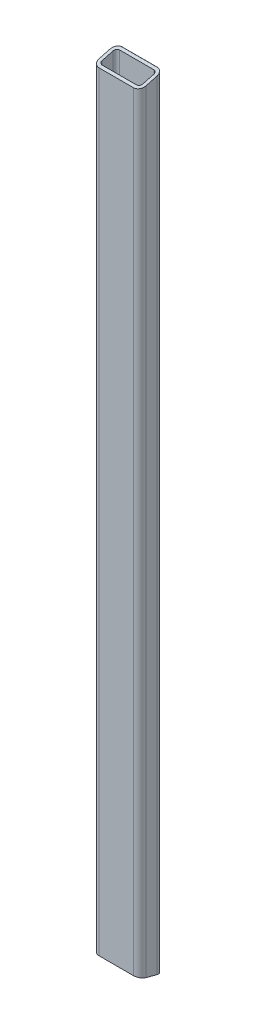
SolidWorks part; units mm, degrees
material "Ст 3 ГОСТ 380-88"
ref_plane "Спереди" through (0, 0, 0) normal (0, 0, 1) x (1, 0, 0)
ref_plane "Сверху" through (0, 0, 0) normal (0, 1, 0) x (1, 0, 0)
ref_plane "Справа" through (0, 0, 0) normal (1, 0, 0) x (0, 0, -1)
sketch "Эскиз1" plane through (0, 0, 0) normal (0, 1, 0) x (1, 0, 0)
  line L0 (-15, 7.5) -> (15, -7.5) construction
  line L1 (-11, 7.5) -> (11, 7.5)
  line L2 (-15, 3.5) -> (-15, -3.5)
  line L3 (-11, -7.5) -> (11, -7.5)
  line L4 (15, 3.5) -> (15, -3.5)
  line L5 (-15, -7.5) -> (15, 7.5) construction
  arc A0 (-15, -3.5) -> (-11, -7.5) centre (-11, -3.5) ccw
  arc A1 (11, -7.5) -> (15, -3.5) centre (11, -3.5) ccw
  arc A2 (11, 7.5) -> (15, 3.5) centre (11, 3.5) cw
  arc A3 (-11, 7.5) -> (-15, 3.5) centre (-11, 3.5) ccw
  point P4 (0, 0)
  dimension "D3" = 4
  dimension "D1" = 30
  dimension "D2" = 15
extrude "Вытянуть-Тонкостенный1" add sketch "Эскиз1" along normal blind 250 and the other way blind 250 thin
chamfer "Фаска1" distance 4 angle 75 2 edges at (0, -250, 7.5) (0, 250, 7.5)
